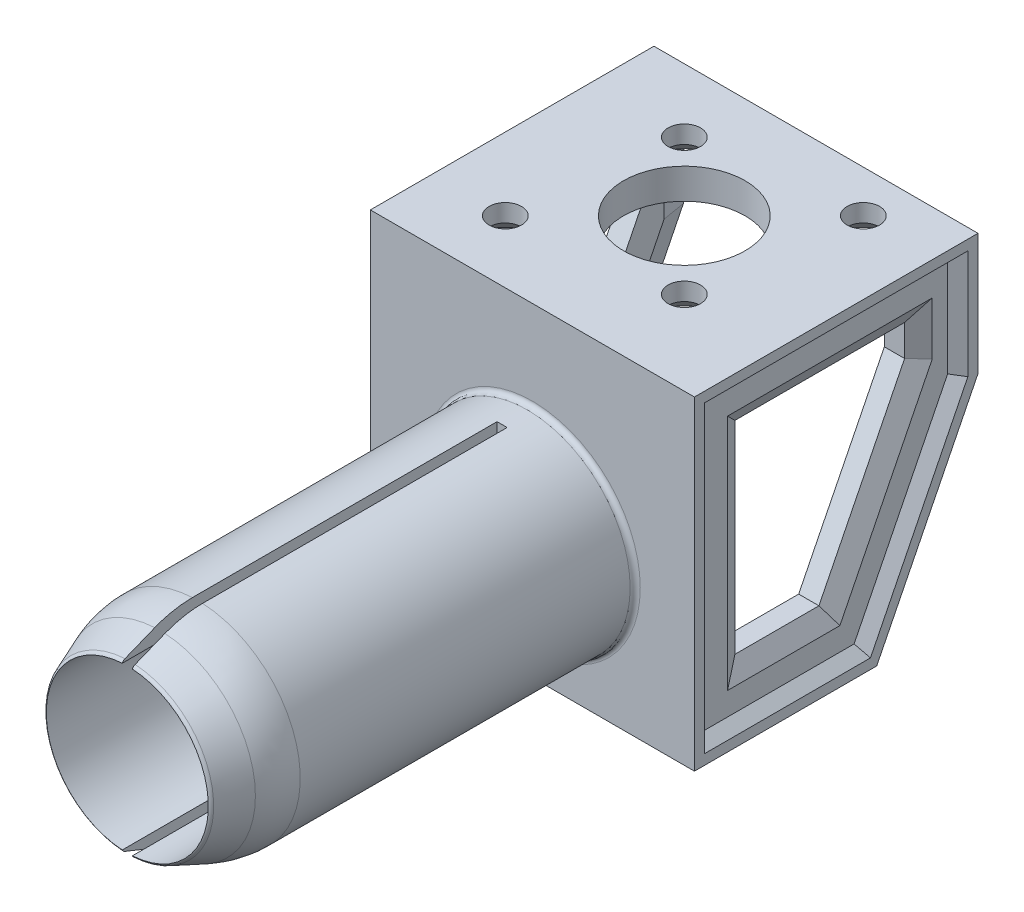
SolidWorks part; units mm, degrees
material "ABS"
ref_plane "Plan de face" through (0, 0, 0) normal (0, 0, 1) x (1, 0, 0)
ref_plane "Plan de dessus" through (0, 0, 0) normal (0, 1, 0) x (1, 0, 0)
ref_plane "Plan de droite" through (0, 0, 0) normal (1, 0, 0) x (0, 0, -1)
sketch "Esquisse1" plane through (0, 0, 0) normal (0, 0, 1) x (1, 0, 0)
  line L0 (0, 16) -> (0, 0) construction
  line L1 (-16, 16) -> (16, 16)
  line L2 (-16, 16) -> (-16, -16)
  line L3 (-16, -16) -> (16, -16)
  line L4 (16, 16) -> (16, -16)
  line L5 (0, 0) -> (16, 0) construction
  dimension "D1" = 32
extrude "Boss.-Extru.1" add sketch "Esquisse1" along normal mid plane 28 contours L1 L4 L3 L2
chamfer "Chanfrein1" distance 20 distance2 10 1 edges at (0, -16, -14) first distance on face at (0, 0, -14)
sketch "Esquisse5" plane through (-16, 0, 0) normal (-1, 0, 0) x (0, 0, 1)
  line L14 (-12, 14) -> (-12, 4.4721)
  line L15 (-12, 4.4721) -> (-2.7639, -14)
  line L16 (-2.7639, -14) -> (12, -14)
  line L17 (12, -14) -> (12, 14)
  line L19 (12, 14) -> (-12, 14)
  line L21 (-12, 14) -> (-12, 4.4721)
  line L22 (-12, 4.4721) -> (-2.7639, -14)
  line L23 (-2.7639, -14) -> (12, -14)
  line L24 (12, -14) -> (12, 14)
  line L26 (12, 14) -> (-12, 14)
  dimension "D1" = 2
extrude "Enlèv. mat.-Extru.1" cut sketch "Esquisse5" against normal blind 1 contours L26 L21 L22 L23 L24 region at (-16, 1.1403, 1.2972)
mirror "Symétrie1" about plane through (0, 0, 0) normal (1, 0, 0) of "Enlèv. mat.-Extru.1"
ref_plane "Plan1" through (0, 8, 0) normal (0, 1, 0) x (1, 0, 0)
ref_plane "Plan2" through (0, 0, 11) normal (0, 0, 1) x (1, 0, 0)
sketch "Esquisse11" plane through (0, 0, 11) normal (0, 0, 1) x (1, 0, 0)
  line L0 (-16, -16) -> (16, -16) construction
  line L1 (-16, -16) -> (16, -16)
  line L2 (-12, 13) -> (-12, -16)
  line L3 (-12, 13) -> (12, 13)
  line L5 (-12, -16) -> (12, -16)
  line L6 (0, -16) -> (0, 15.7047) construction
  line L18 (12, 13) -> (12, -16)
  dimension "D1" = 29
  dimension "D2" = 24
extrude "Enlèv. mat.-Extru.4" cut sketch "Esquisse11" against normal through all contours L3 L1 | L6 L1 L18 L3 region at (-6, -1.5, 11) region at (6, -1.5, 11)
chamfer "Chanfrein41" distance 1 angle 45 10 edges at (16, -4.7639, -7.382) (16, 0, 12) (16, 14, 0) (16, 9.2361, -12) (-16, 0, 12) (-16, -4.7639, -7.382) (-16, 14, 0) (-16, 9.2361, -12) (16, -14, 4.618) (-16, -14, 4.618)
sketch "Esquisse24" plane through (-15, 0, 0) normal (-1, 0, 0) x (0, 0, 1)
  line L0 (-8.75, 6.9164) -> (-8.75, 10)
  line L1 (-8.75, 10) -> (8, 10)
  line L2 (8, 10) -> (8, -10)
  line L4 (12, 14) -> (-12, 14) construction
  line L6 (-8, 10) -> (-8, 5.4164)
  line L10 (-8, 5.4164) -> (-0.2918, -10)
  line L11 (-0.2918, -10) -> (8, -10)
  line L12 (8, -10) -> (8, 10)
  line L13 (8, 10) -> (-8, 10)
  line L14 (-8.75, 6.9164) -> (-0.2918, -10)
  line L15 (-0.2918, -10) -> (8, -10)
  point P0 (8, 7)
  point P1 (-5.5, 6)
  dimension "D2" = 4
  dimension "D1" = 4
extrude "Enlèv. mat.-Extru.13" cut sketch "Esquisse24" against normal through all
chamfer "Chanfrein63" distance 1 angle 60 10 edges at (-15, 8.4582, -8.75) (-15, 10, -0.375) (-15, 0, 8) (-15, -1.5418, -4.5209) (15, 8.4582, -8.75) (15, 10, -0.375) (15, 0, 8) (15, -1.5418, -4.5209) (-15, -10, 3.8541) (15, -10, 3.8541) first distance on face at (-13.5, 8.4582, -8.75) first distance on face at (-13.5, 10, -0.375) first distance on face at (-13.5, 0, 8) first distance on face at (-13.5, -1.5418, -4.5209) first distance on face at (13.5, 8.4582, -8.75) first distance on face at (13.5, 10, -0.375) first distance on face at (13.5, 0, 8) first distance on face at (13.5, -1.5418, -4.5209) first distance on face at (-13.5, -10, 3.8541) first distance on face at (13.5, -10, 3.8541)
ref_plane "Plan3" through (0, 19.5, 0) normal (0, 1, 0) x (1, 0, 0)
sketch "Esquisse32" plane through (0, 0, 14) normal (0, 0, 1) x (1, 0, 0)
  line L0 (0, 0) -> (0, -3) construction
  circle A0 centre (0, -3) radius 8
  circle A1 centre (0, -3) radius 10.15
  dimension "D1" = 16
  dimension "D3" = 20.3
  dimension "D2" = 3
extrude "Boss.-Extru.2" add sketch "Esquisse32" along normal blind 40
sketch "Esquisse35" plane through (0, 0, 54) normal (0, 0, 1) x (1, 0, 0)
  line L0 (0.5, 4.9844) -> (0.5, 7.1377)
  line L1 (-0.5, -10.9844) -> (-0.5, -13.1377)
  line L2 (-0.5, 4.9844) -> (-0.5, 7.1377)
  line L3 (0.5, -10.9844) -> (0.5, -13.1377)
  line L5 (0.5, 5) -> (0.5, 7.15) construction
  line L6 (-0.5, 5) -> (-0.5, 7.15) construction
  line L7 (0.5, -11) -> (0.5, -13.15) construction
  line L8 (-0.5, -11) -> (-0.5, -13.15) construction
  line L10 (0, 5) -> (0, 7.15) construction
  line L11 (0, -11) -> (0, -13.15) construction
  circle A0 centre (0, -3) radius 10.15 construction
  circle A1 centre (0, -3) radius 8 construction
  circle A2 centre (0, -3) radius 10.15
  circle A3 centre (0, -3) radius 8
  circle M1 centre (0, -3) radius 10.15
  circle M2 centre (0, -3) radius 8
  dimension "D1" = 0.5
  dimension "D2" = 0.5
extrude "Enlèv. mat.-Extru.17" cut sketch "Esquisse35" against normal blind 37 contours L2 L0 M2 M1 | L3 L1 M2 M1 region at (0, 6.0703, 54) region at (0, -12.0703, 54)
ref_plane "Plan5" through (-10.15, 0, 0) normal (-1, 0, 0) x (0, 0, 1)
chamfer "Chanfrein50" distance 5 distance2 2 2 edges at (10.15, -3, 54) (-10.15, -3, 54) first distance on face at (10.15, -3, 14)
fillet "Congé4" radius 0.5 2 edges at (-8.15, -3, 54) (8.15, -3, 54)
fillet "Congé5" radius 10 2 edges at (10.15, -3, 49) (-10.15, -3, 49)
fillet "Congé6" radius 0.5 1 edges at (10.15, -3, 14)
sketch "Esquisse71" plane through (0, 13, 0) normal (0, -1, 0) x (1, 0, 0)
  line L0 (-12, 11) -> (12, -13) construction
  line L1 (-12, -13) -> (12, 11) construction
  circle A0 centre (0, -1) radius 6
  circle A1 centre (8.8388, -9.8388) radius 1.6
  circle A2 centre (-8.8388, 7.8388) radius 1.6
  circle A3 centre (-6.7175, -7.7175) radius 1.6
  circle A4 centre (6.7175, 5.7175) radius 1.6
  dimension "D1" = 12
  dimension "D2" = 3.2
  dimension "D4" = 3.2
  dimension "D3" = 12.5
  dimension "D5" = 9.5
extrude "Enlèv. mat.-Extru.45" cut sketch "Esquisse71" against normal up to next
chamfer "Chanfrein64" distance 1.25 angle 45 4 edges at (8.8388, 13, -11.4388) (6.7175, 13, 7.3175) (-8.8388, 13, 9.4388) (-6.7175, 13, -9.3175)
chamfer "Chamfer1" distance 3 1 edges at (8, -3, 14)
sketch "Sketch4" plane through (0, 0, 14) normal (0, 0, 1) x (1, 0, 0)
  circle A0 centre (0, -3) radius 5
extrude "Cut-Extrude1" cut sketch "Sketch4" against normal through all contours A0
fillet "Fillet2" radius 3 1 edges at (5, -3, 11)
chamfer "Chamfer2" distance 3 angle 20 6 edges at (12, -16, 3.5) (12, -6, -9) (12, 8.5, -14) (-12, 8.5, -14) (-12, -6, -9) (-12, -16, 3.5) first distance on face at (12, 1.3833, -0.3584) first distance on face at (-12, 1.3833, -0.3584)
